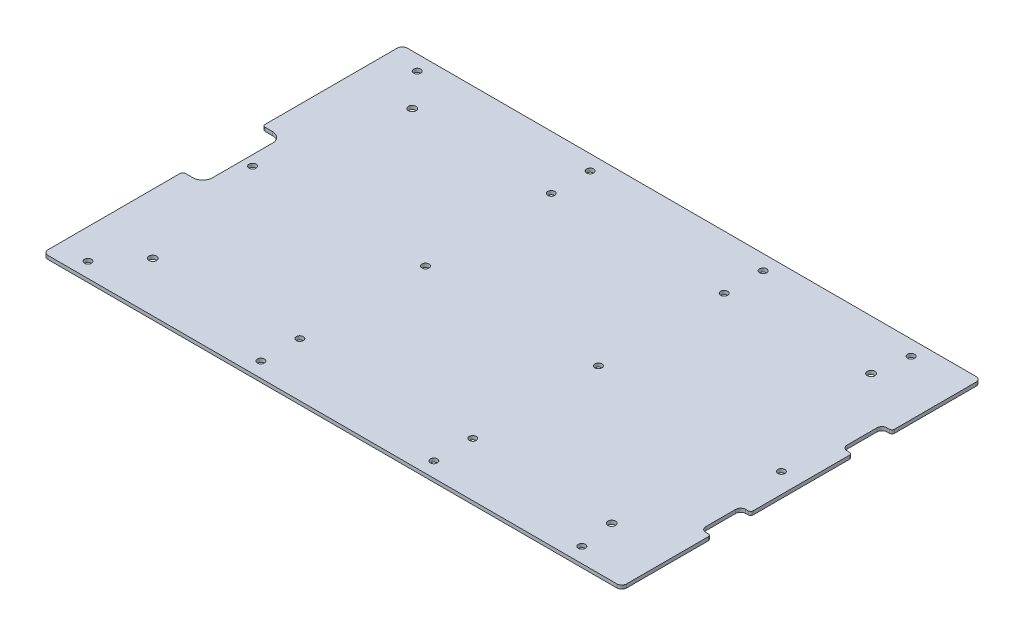
SolidWorks part; units mm, degrees
material "1060 Alloy"
ref_plane "Front" through (0, 0, 0) normal (0, 0, 1) x (1, 0, 0)
ref_plane "Top" through (0, 0, 0) normal (0, 1, 0) x (1, 0, 0)
ref_plane "Right" through (0, 0, 0) normal (1, 0, 0) x (0, 0, -1)
sketch "Sketch1" plane through (0, 0, 0) normal (0, 1, 0) x (1, 0, 0)
  line L0 (-55.0333, 0) -> (-165.1, 0) construction
  line L1 (-180.975, 114.3) -> (180.975, 114.3)
  line L2 (-184.15, 111.125) -> (-184.15, -111.125)
  line L3 (-180.975, -114.3) -> (180.975, -114.3)
  line L4 (184.15, 111.125) -> (184.15, -111.125)
  line L5 (-184.15, 114.3) -> (184.15, -114.3) construction
  line L6 (-184.15, -114.3) -> (184.15, 114.3) construction
  line L7 (-165.1, -104.775) -> (165.1, -104.775) construction
  line L8 (-165.1, -104.775) -> (-165.1, 104.775) construction
  line L9 (-165.1, 104.775) -> (165.1, 104.775) construction
  line L10 (165.1, -104.775) -> (165.1, 104.775) construction
  line L11 (-165.1, -104.775) -> (165.1, 104.775) construction
  line L12 (-165.1, 104.775) -> (165.1, -104.775) construction
  line L13 (-55.0333, -104.775) -> (55.0333, -104.775) construction
  line L14 (-55.0333, -104.775) -> (-55.0333, 104.775) construction
  line L15 (-55.0333, 104.775) -> (55.0333, 104.775) construction
  line L16 (55.0333, -104.775) -> (55.0333, 104.775) construction
  line L17 (-55.0333, -104.775) -> (55.0333, 104.775) construction
  line L18 (-55.0333, 104.775) -> (55.0333, -104.775) construction
  line L19 (55.0333, 0) -> (165.1, 0) construction
  line L20 (-55.0333, 0) -> (55.0333, 0) construction
  line L31 (-55.0291, 80.01) -> (55.0291, 80.01) construction
  line L32 (149.225, -104.775) -> (149.225, 104.775) construction
  line L33 (-55.0291, 80.01) -> (-55.0291, -80.01) construction
  line L34 (-55.0291, -80.01) -> (55.0291, -80.01) construction
  line L35 (55.0291, 80.01) -> (55.0291, -80.01) construction
  line L36 (-55.0291, 80.01) -> (55.0291, -80.01) construction
  line L37 (-55.0291, -80.01) -> (55.0291, 80.01) construction
  circle A0 centre (-165.1, 104.775) radius 2.2479
  circle A1 centre (-55.0333, 104.775) radius 2.2479
  circle A2 centre (55.0333, 104.775) radius 2.2479
  circle A3 centre (165.1, 104.775) radius 2.2479 construction
  circle A4 centre (165.1, -104.775) radius 2.2479 construction
  circle A5 centre (55.0333, -104.775) radius 2.2479
  circle A6 centre (-55.0333, -104.775) radius 2.2479
  circle A7 centre (-165.1, -104.775) radius 2.2479
  circle A12 centre (-55.0333, 0) radius 2.2479
  circle A13 centre (55.0333, 0) radius 2.2479
  arc A14 (184.15, 111.125) -> (180.975, 114.3) centre (180.975, 111.125) ccw
  arc A15 (184.15, -111.125) -> (180.975, -114.3) centre (180.975, -111.125) cw
  arc A16 (-180.975, -114.3) -> (-184.15, -111.125) centre (-180.975, -111.125) cw
  arc A17 (-180.975, 114.3) -> (-184.15, 111.125) centre (-180.975, 111.125) ccw
  circle A24 centre (149.225, -104.775) radius 2.2479
  circle A25 centre (149.225, 104.775) radius 2.2479
  circle A26 centre (55.0291, -80.01) radius 2.2479
  circle A27 centre (-55.0291, -80.01) radius 2.2479
  circle A28 centre (-55.0291, 80.01) radius 2.2479
  circle A29 centre (55.0291, 80.01) radius 2.2479
  circle A30 centre (171.45, 0) radius 2.2479
  circle A31 centre (-165.1, 0) radius 2.2479
  circle A32 centre (-146.05, 82.55) radius 2.4574 construction
  circle A33 centre (-146.05, 82.55) radius 2.4575
  circle A34 centre (146.05, 82.55) radius 2.4574 construction
  circle A35 centre (146.05, 82.55) radius 2.4575
  circle A36 centre (-146.05, -82.55) radius 2.4574 construction
  circle A37 centre (-146.05, -82.55) radius 2.4575
  circle A38 centre (146.05, -82.55) radius 2.4574 construction
  circle A39 centre (146.05, -82.55) radius 2.4575
  point P0 (0, 0)
  point P6 (0, 0)
  point P11 (0, 0)
  point P28 (0, 0)
  point P29 (0, 0)
  point P32 (0, 0)
  dimension "D5" = 4.4958
  dimension "D8" = 4.4958
  dimension "D11" = 3.175
  dimension "D10" = 12.7
  dimension "D12" = 19.05
  dimension "D13" = 110.0667
  dimension "D1" = 368.3
  dimension "D2" = 228.6
  dimension "D3" = 9.525
  dimension "D4" = 19.05
  dimension "D6" = 160.02
  dimension "D7" = 34.925
  dimension "D9" = 110.0582
extrude "Boss-Extrude1" add sketch "Sketch1" along normal blind 2.286
sketch "Sketch2" plane through (0, 0, 0) normal (0, -1, 0) x (1, 0, 0)
  line L5 (184.15, 111.125) -> (184.15, -111.125) construction
  line L6 (184.15, 57.658) -> (180.975, 57.658)
  line L7 (184.15, 57.658) -> (184.15, 32.258)
  line L8 (184.15, 32.258) -> (180.975, 32.258)
  line L9 (177.8, 54.483) -> (177.8, 35.433)
  line L10 (-184.15, 0) -> (184.15, 0) construction
  line L11 (-184.15, -111.125) -> (-184.15, 111.125) construction
  line L13 (177.8, 44.958) -> (184.15, 44.958) construction
  line L14 (184.15, -32.258) -> (180.975, -32.258)
  line L15 (184.15, -57.658) -> (184.15, -32.258)
  line L16 (177.8, -54.483) -> (177.8, -35.433)
  line L17 (184.15, -57.658) -> (180.975, -57.658)
  line L19 (-184.15, 25.4) -> (-177.8, 25.4)
  line L20 (-184.15, 25.4) -> (-184.15, -25.4)
  line L21 (-184.15, -25.4) -> (-177.8, -25.4)
  line L22 (-171.45, 19.05) -> (-171.45, -19.05)
  arc A0 (180.975, -57.658) -> (177.8, -54.483) centre (180.975, -54.483) cw
  arc A1 (177.8, -35.433) -> (180.975, -32.258) centre (180.975, -35.433) cw
  arc A2 (177.8, 35.433) -> (180.975, 32.258) centre (180.975, 35.433) ccw
  arc A3 (177.8, 54.483) -> (180.975, 57.658) centre (180.975, 54.483) cw
  arc A4 (-171.45, -19.05) -> (-177.8, -25.4) centre (-177.8, -19.05) cw
  arc A5 (-171.45, 19.05) -> (-177.8, 25.4) centre (-177.8, 19.05) ccw
  point P12 (184.15, 0)
  point P20 (177.8, -57.658)
  point P23 (177.8, -32.258)
  point P26 (177.8, 32.258)
  point P29 (177.8, 57.658)
  point P38 (-171.45, 25.4)
  point P39 (0, 0)
  point P40 (0, 0)
  point P41 (0, 0)
  point P42 (189.103, 0)
  point P43 (0, 0)
  dimension "D4" = 3.175
  dimension "D7" = 6.35
  dimension "D1" = 25.4
  dimension "D2" = 44.958
  dimension "D3" = 6.35
  dimension "D5" = 50.8
  dimension "D6" = 12.7
extrude "Cut-Extrude1" cut sketch "Sketch2" against normal through all
fillet "Fillet1" radius 1.5875 6 edges at (184.15, 1.143, -57.658) (184.15, 1.143, -32.258) (184.15, 1.143, 32.258) (184.15, 1.143, 57.658) (-184.15, 1.143, -25.4) (-184.15, 1.143, 25.4)
sketch "Sketch3" plane through (0, 2.286, 0) normal (0, 1, 0) x (1, 0, 0)
  line L0 (-198.0256, -111.0509) -> (-198.0256, 117.5491)
  line L1 (204.2781, -126.2696) -> (-1014.9219, -126.2696)
  line L2 (204.2781, -126.2696) -> (204.2781, 1092.9304)
  line L3 (204.2781, 1092.9304) -> (-1014.9219, 1092.9304)
  line L4 (-1014.9219, -126.2696) -> (-1014.9219, 1092.9304)
  line L5 (182.9744, -111.0509) -> (-185.3256, -111.0509)
  line L6 (182.9744, -111.0509) -> (182.9744, 117.5491)
  line L7 (182.9744, 117.5491) -> (-185.3256, 117.5491)
  line L8 (-185.3256, -111.0509) -> (-185.3256, 117.5491)
  line L9 (-198.0256, -111.0509) -> (-566.3256, -111.0509)
  line L10 (-566.3256, -111.0509) -> (-566.3256, 117.5491)
  line L11 (-198.0256, 117.5491) -> (-566.3256, 117.5491)
  line L12 (-579.0256, -111.0509) -> (-579.0256, 117.5491)
  line L13 (-579.0256, -111.0509) -> (-947.3256, -111.0509)
  line L14 (-947.3256, -111.0509) -> (-947.3256, 117.5491)
  line L15 (-579.0256, 117.5491) -> (-947.3256, 117.5491)
  line L16 (-198.0256, 130.2491) -> (-198.0256, 358.8491)
  line L17 (-198.0256, 130.2491) -> (-566.3256, 130.2491)
  line L18 (-566.3256, 130.2491) -> (-566.3256, 358.8491)
  line L19 (-198.0256, 358.8491) -> (-566.3256, 358.8491)
  line L20 (-579.0256, 130.2491) -> (-579.0256, 358.8491)
  line L21 (-579.0256, 130.2491) -> (-947.3256, 130.2491)
  line L22 (-947.3256, 130.2491) -> (-947.3256, 358.8491)
  line L23 (-579.0256, 358.8491) -> (-947.3256, 358.8491)
  line L24 (-198.0256, 371.5491) -> (-198.0256, 600.1491)
  line L25 (-198.0256, 371.5491) -> (-566.3256, 371.5491)
  line L26 (-566.3256, 371.5491) -> (-566.3256, 600.1491)
  line L27 (-198.0256, 600.1491) -> (-566.3256, 600.1491)
  line L28 (-579.0256, 371.5491) -> (-579.0256, 600.1491)
  line L29 (-579.0256, 371.5491) -> (-947.3256, 371.5491)
  line L30 (-947.3256, 371.5491) -> (-947.3256, 600.1491)
  line L31 (-579.0256, 600.1491) -> (-947.3256, 600.1491)
  line L32 (-198.0256, 612.8491) -> (-198.0256, 841.4491)
  line L33 (-198.0256, 612.8491) -> (-566.3256, 612.8491)
  line L34 (-566.3256, 612.8491) -> (-566.3256, 841.4491)
  line L35 (-198.0256, 841.4491) -> (-566.3256, 841.4491)
  line L36 (-579.0256, 612.8491) -> (-579.0256, 841.4491)
  line L37 (-579.0256, 612.8491) -> (-947.3256, 612.8491)
  line L38 (-947.3256, 612.8491) -> (-947.3256, 841.4491)
  line L39 (-579.0256, 841.4491) -> (-947.3256, 841.4491)
  line L40 (-198.0256, 854.1491) -> (-198.0256, 1082.7491)
  line L41 (-198.0256, 854.1491) -> (-566.3256, 854.1491)
  line L42 (-566.3256, 854.1491) -> (-566.3256, 1082.7491)
  line L43 (-198.0256, 1082.7491) -> (-566.3256, 1082.7491)
  line L44 (-579.0256, 854.1491) -> (-579.0256, 1082.7491)
  line L45 (-579.0256, 854.1491) -> (-947.3256, 854.1491)
  line L46 (-947.3256, 854.1491) -> (-947.3256, 1082.7491)
  line L47 (-579.0256, 1082.7491) -> (-947.3256, 1082.7491)
  line L48 (182.9744, 130.2491) -> (182.9744, 358.8491)
  line L49 (182.9744, 130.2491) -> (-185.3256, 130.2491)
  line L50 (-185.3256, 130.2491) -> (-185.3256, 358.8491)
  line L51 (182.9744, 358.8491) -> (-185.3256, 358.8491)
  line L52 (182.9744, 371.5491) -> (182.9744, 600.1491)
  line L53 (182.9744, 371.5491) -> (-185.3256, 371.5491)
  line L54 (-185.3256, 371.5491) -> (-185.3256, 600.1491)
  line L55 (182.9744, 600.1491) -> (-185.3256, 600.1491)
  line L56 (182.9744, 612.8491) -> (182.9744, 841.4491)
  line L57 (182.9744, 612.8491) -> (-185.3256, 612.8491)
  line L58 (-185.3256, 612.8491) -> (-185.3256, 841.4491)
  line L59 (182.9744, 841.4491) -> (-185.3256, 841.4491)
  line L60 (182.9744, 854.1491) -> (182.9744, 1082.7491)
  line L61 (182.9744, 854.1491) -> (-185.3256, 854.1491)
  line L62 (-185.3256, 854.1491) -> (-185.3256, 1082.7491)
  line L63 (182.9744, 1082.7491) -> (-185.3256, 1082.7491)
  dimension "D1" = 1219.2
  dimension "D2" = 1219.2
  dimension "D3" = 368.3
  dimension "D4" = 228.6
  dimension "D5" = 3
  dimension "D6" = 5
